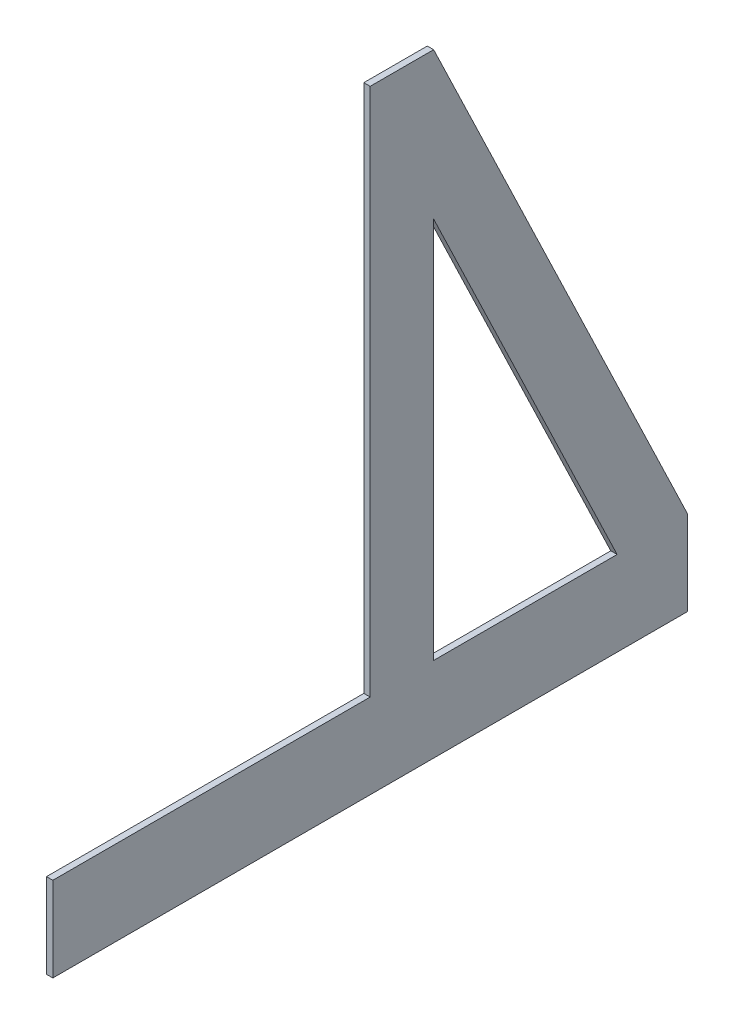
SolidWorks part; units mm, degrees
material "Клен"
ref_plane "Спереди" through (0, 0, 0) normal (0, 0, 1) x (1, 0, 0)
ref_plane "Сверху" through (0, 0, 0) normal (0, 1, 0) x (1, 0, 0)
ref_plane "Справа" through (0, 0, 0) normal (1, 0, 0) x (0, 0, -1)
sketch "боковина" plane through (0, 0, 0) normal (1, 0, 0) x (0, 0, -1)
  line L0 (-593.8462, -244.4615) -> (6.1538, -244.4615)
  line L1 (6.1538, -244.4615) -> (6.1538, -164.4615)
  line L2 (6.1538, -164.4615) -> (-233.8462, 335.5385)
  line L3 (-233.8462, 335.5385) -> (-293.8462, 335.5385)
  line L4 (-293.8462, 335.5385) -> (-293.8462, -164.4615)
  line L5 (-293.8462, -164.4615) -> (-593.8462, -164.4615)
  line L6 (-593.8462, -164.4615) -> (-593.8462, -244.4615)
  line L7 (-233.8462, -164.4615) -> (-60.4002, -164.4615)
  line L8 (-60.4002, -164.4615) -> (-233.8462, 196.8842)
  line L9 (-233.8462, 196.8842) -> (-233.8462, -164.4615)
  dimension "D1" = 80
  dimension "D2" = 60
  dimension "D3" = 600
  dimension "D6" = 300
  dimension "D7" = 60
  dimension "D8" = 60
  dimension "D4" = 500
  dimension "D5" = 80
extrude "Бобышка-боковина" add sketch "боковина" along normal blind 6
equation "\"D2@боковина\" = \"bottom_line\""
equation "\"D7@боковина\" = \"bottom_line\""
equation "\"D8@боковина\" = \"bottom_line\""
equation "\"sheet_thickness\"= 6"
equation "\"bottom_line\"= 60"
equation "\"width_space\"= 500"
equation "\"D5@боковина\"=\"D1@боковина\""
